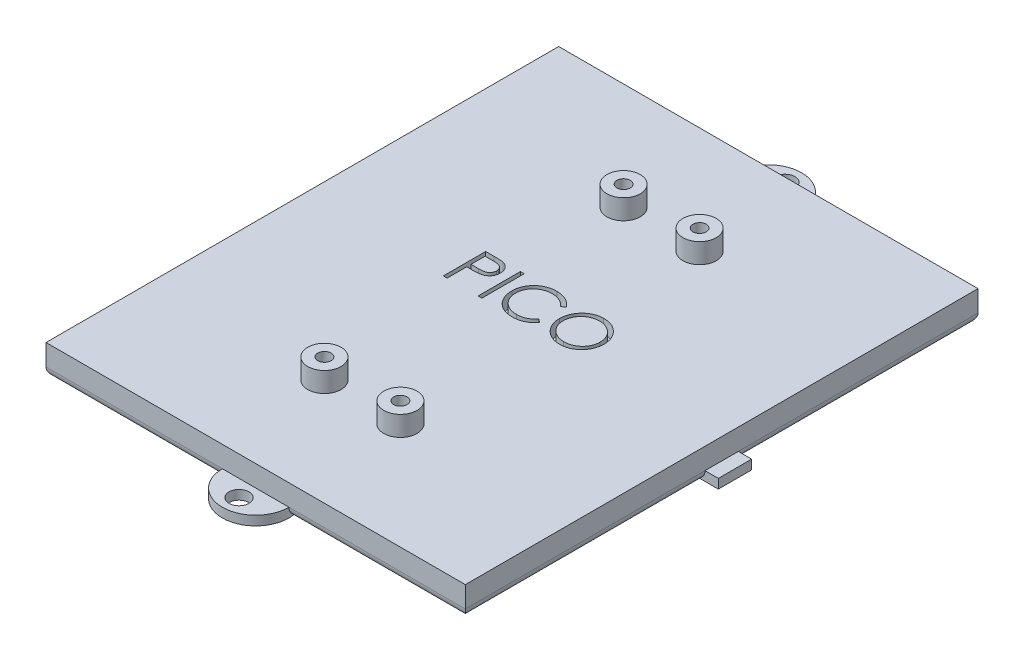
SolidWorks part; units mm, degrees
ref_plane "Front Plane" through (0, 0, 0) normal (0, 0, 1) x (1, 0, 0)
ref_plane "Top Plane" through (0, 0, 0) normal (0, 1, 0) x (1, 0, 0)
ref_plane "Right Plane" through (0, 0, 0) normal (1, 0, 0) x (0, 0, -1)
sketch "Sketch1" plane through (0, 0, 0) normal (0, 1, 0) x (1, 0, 0)
  line L0 (-31.45, 38.45) -> (31.45, 38.45)
  line L5 (-31.45, 38.45) -> (-31.45, -38.45)
  line L6 (-31.45, -38.45) -> (31.45, -38.45)
  line L7 (31.45, 38.45) -> (31.45, -38.45)
  point P11 (-31.45, 0)
  point P12 (0, -38.45)
  dimension "D3" = 76.9
  dimension "D4" = 62.9
extrude "Boss-Extrude1" add sketch "Sketch1" along normal blind 4.575
sketch "Sketch4" plane through (0, 0, 0) normal (0, 1, 0) x (1, 0, 0)
  line L0 (-5, -38.45) -> (5, -38.45)
  line L2 (-31.45, -38.45) -> (31.45, -38.45) construction
  line L4 (0, -38.45) -> (0, -43.45) construction
  arc A0 (-5, -38.45) -> (5, -38.45) centre (0, -38.45) ccw
  circle A2 centre (0, -40.95) radius 1.5
  dimension "D2" = 3
  dimension "D3" = 5
extrude "Boss-Extrude3" add sketch "Sketch4" along normal blind 1.4
mirror "Mirror1" about plane through (0, 0, 0) normal (0, 0, 1) of "Boss-Extrude3"
sketch "Sketch6" plane through (-31.45, 0, 0) normal (-1, 0, 0) x (0, 0, 1)
  line L0 (-38.45, 0) -> (38.45, 0) construction
  line L1 (-2.5, 0) -> (2.5, 0)
  line L2 (-2.5, 0) -> (-2.5, 1.4)
  line L3 (-2.5, 1.4) -> (2.5, 1.4)
  line L4 (2.5, 0) -> (2.5, 1.4)
  line L5 (43.45, 1.4) -> (38.45, 1.4) construction
  point P6 (0, 0)
  point P7 (0, 1.4)
  dimension "D1" = 5
extrude "Boss-Extrude4" add sketch "Sketch6" along normal blind 2
mirror "Mirror2" about plane through (0, 0, 0) normal (1, 0, 0) of "Boss-Extrude4"
fillet "Fillet1" radius 1.4 8 edges at (-18.225, 0, 38.45) (18.225, 0, 38.45) (31.45, 0, -20.475) (31.45, 0, 20.475) (18.225, 0, -38.45) (-18.225, 0, -38.45) (-31.45, 0, 20.475) (-31.45, 0, -20.475)
sketch "Sketch2" plane through (0, 4.575, 0) normal (0, 1, 0) x (1, 0, 0)
  line L1 (-5.7, 22.4375) -> (5.7, 22.4375) construction
  line L2 (5.7, 22.4375) -> (5.7, -22.4375) construction
  line L3 (5.7, -22.4375) -> (-5.7, -22.4375) construction
  line L4 (-5.7, -22.4375) -> (-5.7, 22.4375) construction
  circle A8 centre (-5.7, 22.4375) radius 1
  circle A9 centre (5.7, 22.4375) radius 1
  circle A10 centre (-5.7, -22.4375) radius 1
  circle A11 centre (5.7, -22.4375) radius 1
  circle A12 centre (-5.7, -22.4375) radius 2.5
  circle A13 centre (5.7, -22.4375) radius 2.5
  circle A14 centre (5.7, 22.4375) radius 2.5
  circle A15 centre (-5.7, 22.4375) radius 2.5
  point P8 (5.7, 0)
  point P9 (0, 22.4375)
  dimension "D1" = 2
  dimension "D4" = 1.5
  dimension "D2" = 44.875
  dimension "D3" = 11.4
extrude "Screw_Holes" add sketch "Sketch2" along normal blind 3
sketch "Sketch3" plane through (0, 4.575, 0) normal (0, 1, 0) x (1, 0, 0)
  circle A0 centre (5.7, -22.4375) radius 1
  circle A1 centre (-5.7, -22.4375) radius 1
  circle A2 centre (-5.7, 22.4375) radius 1
  circle A3 centre (5.7, 22.4375) radius 1
  circle A6 centre (-5.7, -22.4375) radius 1 construction
extrude "Cut-Extrude1" cut sketch "Sketch3" against normal offset from surface (3.575 mm away) 1 up to face at (0, 0, 0)
sketch "Sketch5" plane through (0, 4.575, 0) normal (0, 1, 0) x (1, 0, 0)
  line L0 (-15, 0) -> (15, 0) construction
  text T0 "PICO\r\n" font "Century Gothic" height in points 24
  point P6 (0, 0)
  dimension "D1" = 30
extrude "Letters" cut sketch "Sketch5" against normal blind 2
